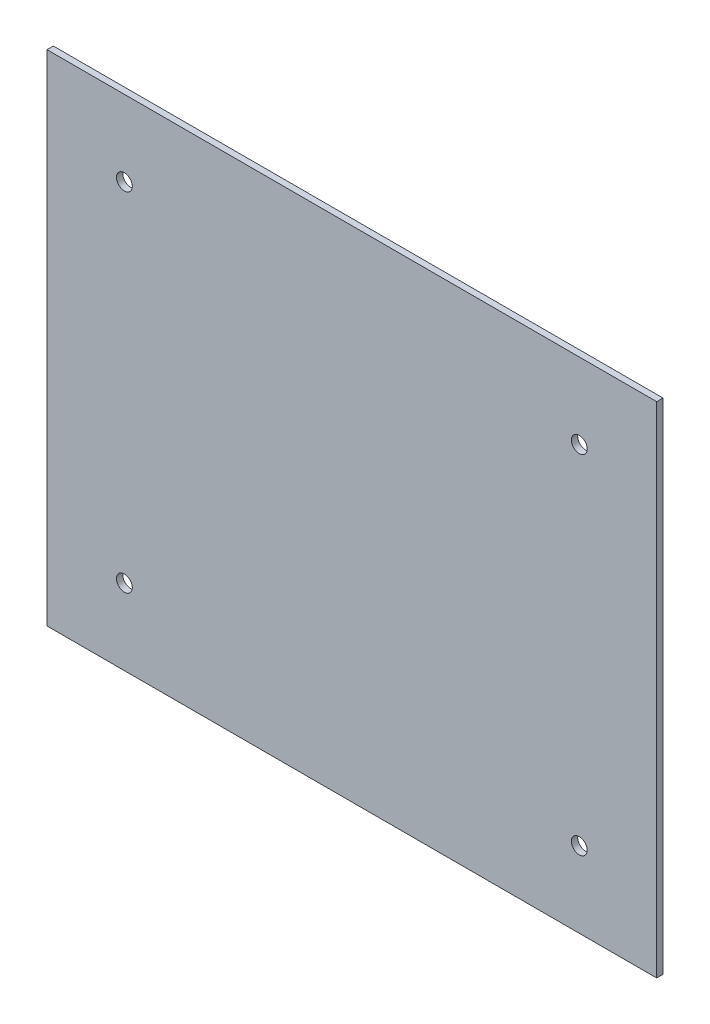
SolidWorks part; units mm, degrees
material "201 Annealed Stainless Steel (SS)"
ref_plane "Front Plane" through (0, 0, 0) normal (0, 0, 1) x (1, 0, 0)
ref_plane "Top Plane" through (0, 0, 0) normal (0, 1, 0) x (1, 0, 0)
ref_plane "Right Plane" through (0, 0, 0) normal (1, 0, 0) x (0, 0, -1)
sketch "Sketch1" plane through (0, 0, 0) normal (0, 0, 1) x (1, 0, 0)
  line L0 (0, 0) -> (0, -146.4794) construction
  line L1 (-96.5, 79) -> (96.5, 79)
  line L2 (-96.5, 79) -> (-96.5, -79)
  line L3 (-96.5, -79) -> (96.5, -79)
  line L4 (96.5, 79) -> (96.5, -79)
  line L5 (-96.5, 79) -> (96.5, -79) construction
  line L6 (-96.5, -79) -> (96.5, 79) construction
  line L7 (0, 0) -> (-417.8368, 0) construction
  circle A0 centre (0, 55) radius 3
  circle A1 centre (-372, 55) radius 3
  circle A2 centre (-372, -55) radius 3
  circle A3 centre (0, -55) radius 3
  circle A4 centre (372, -55) radius 3
  circle A5 centre (372, 55) radius 3
  circle A6 centre (-372, 55) radius 2.5 construction
  point P0 (0, 0)
  dimension "D3" = 6
  dimension "D5" = 21
  dimension "D7" = 272.5
  dimension "D1" = 158
  dimension "D2" = 193
extrude "Boss-Extrude1" add sketch "Sketch1" along normal mid plane 2
other "DeleteFace1" face at (3, 55, 1) face at (-3, -55, 1) and patch yes
sketch "Sketch2" [suppressed] plane through (0, 0, 1) normal (0, 0, 1) x (1, 0, 0)
  line L0 (265.7847, 0) -> (416.352, 0) construction
  line L5 (293.206, -45.5) -> (314.206, -45.5)
  line L6 (293.206, -45.5) -> (293.206, -14.5)
  line L11 (293.206, -14.5) -> (314.206, -14.5)
  line L12 (50.7847, -22.5) -> (95.7847, -22.5)
  line L13 (-93.5, 36.6025) -> (-110.25, 36.6025)
  line L14 (-110.25, 36.6025) -> (-110.25, -45.8975)
  line L15 (-110.25, -45.8975) -> (-49.75, -45.8975)
  line L16 (-49.75, -45.8975) -> (-49.75, 36.6025)
  line L17 (-49.75, 36.6025) -> (-66.5, 36.6025)
  line L18 (-93.5, 36.6025) -> (-110.25, 36.6025)
  line L19 (-110.25, 36.6025) -> (-110.25, -45.8975)
  line L20 (-110.25, -45.8975) -> (-49.75, -45.8975)
  line L21 (-49.75, -45.8975) -> (-49.75, 36.6025)
  line L22 (-49.75, 36.6025) -> (-66.5, 36.6025)
  line L23 (50.7847, 22.5) -> (50.7847, -22.5)
  line L24 (95.7847, 22.5) -> (50.7847, 22.5)
  line L25 (95.7847, -22.5) -> (95.7847, 22.5)
  line L26 (50.7847, -22.5) -> (95.7847, -22.5)
  line L27 (50.7847, 22.5) -> (50.7847, -22.5)
  line L28 (95.7847, 22.5) -> (50.7847, 22.5)
  line L29 (95.7847, -22.5) -> (95.7847, 22.5)
  line L30 (135.7847, -22.5) -> (180.7847, -22.5)
  line L31 (135.7847, 22.5) -> (135.7847, -22.5)
  line L32 (180.7847, 22.5) -> (135.7847, 22.5)
  line L33 (180.7847, -22.5) -> (180.7847, 22.5)
  line L34 (135.7847, -22.5) -> (180.7847, -22.5)
  line L35 (135.7847, 22.5) -> (135.7847, -22.5)
  line L36 (180.7847, 22.5) -> (135.7847, 22.5)
  line L37 (180.7847, -22.5) -> (180.7847, 22.5)
  line L38 (220.7847, -22.5) -> (265.7847, -22.5)
  line L39 (220.7847, 22.5) -> (220.7847, -22.5)
  line L40 (265.7847, 22.5) -> (220.7847, 22.5)
  line L41 (265.7847, -22.5) -> (265.7847, 22.5)
  line L42 (220.7847, -22.5) -> (265.7847, -22.5)
  line L43 (220.7847, 22.5) -> (220.7847, -22.5)
  line L44 (265.7847, 22.5) -> (220.7847, 22.5)
  line L45 (265.7847, -22.5) -> (265.7847, 22.5)
  line L46 (314.206, -45.5) -> (314.206, -14.5)
  line L47 (293.206, -45.5) -> (314.206, -14.5) construction
  line L48 (293.206, -14.5) -> (314.206, -45.5) construction
  line L49 (83.36, 0) -> (-83.36, 0) construction
  line L104 (293.206, -45.5) -> (314.206, -45.5)
  line L105 (293.206, -14.5) -> (293.206, -45.5)
  line L106 (314.206, -14.5) -> (293.206, -14.5)
  line L107 (314.206, -45.5) -> (314.206, -14.5)
  line L108 (293.206, -45.5) -> (314.206, -45.5) construction
  line L109 (293.206, -14.5) -> (293.206, -45.5) construction
  line L110 (314.206, -14.5) -> (293.206, -14.5) construction
  line L111 (314.206, -45.5) -> (314.206, -14.5) construction
  line L165 (-150.5, -45.5) -> (-129.5, -45.5)
  line L166 (-150.5, -14.5) -> (-150.5, -45.5)
  line L167 (-129.5, -14.5) -> (-150.5, -14.5)
  line L168 (-129.5, -45.5) -> (-129.5, -14.5)
  line L169 (-150.5, -45.5) -> (-129.5, -45.5)
  line L170 (-150.5, -14.5) -> (-150.5, -45.5)
  line L171 (-129.5, -14.5) -> (-150.5, -14.5)
  line L172 (-129.5, -45.5) -> (-129.5, -14.5)
  circle A0 centre (303.706, 30) radius 11
  arc A1 (-66.5, 36.6025) -> (-93.5, 36.6025) centre (-80, 35.5625) ccw
  arc A2 (-66.5, 36.6025) -> (-93.5, 36.6025) centre (-80, 35.5625) ccw
  point P25 (303.706, -30)
  dimension "D7" = 22
  dimension "D1" = 0
  dimension "D2" = 0
  dimension "D8" = 30
  dimension "D9" = 30
  dimension "D3" = 0
  dimension "D4" = 0
  dimension "D5" = 0
  dimension "D6" = 0
extrude "Cut-Extrude1" [suppressed] cut sketch "Sketch2" against normal through all
sketch "Sketch3" plane through (0, 0, 1) normal (0, 0, 1) x (1, 0, 0)
  line L0 (0, 0) -> (0, -109.0497) construction
  circle A0 centre (-72, 55) radius 2.5
  circle A1 centre (72, -55) radius 2.5
  circle A2 centre (72, -55) radius 2.5
  circle A3 centre (72, 55) radius 2.5
  circle A4 centre (72, 55) radius 2.5
  circle A5 centre (-72, -55) radius 2.5
  dimension "D1" = 0
  dimension "D2" = 0
extrude "Cut-Extrude2" cut sketch "Sketch3" against normal through all
delete or keep bodies "Body-Delete/Keep 1" type delete bodies bodies 102 103 104 105
other "DeleteFace2" [suppressed]
sketch "Sketch4" [suppressed] plane through (0, 0, 1) normal (0, 0, 1) x (1, 0, 0)
  line L1 (-44.8038, 33) -> (-55.1962, 33) construction
  line L2 (-55.1962, 33) -> (-60.3923, 24) construction
  line L3 (-60.3923, 24) -> (-55.1962, 15) construction
  line L4 (-55.1962, 15) -> (-44.8038, 15) construction
  line L5 (-44.8038, 15) -> (-39.6077, 24) construction
  line L6 (-39.6077, 24) -> (-44.8038, 33) construction
  line L9 (58.2272, -36.75) -> (41.7728, -36.75) construction
  line L10 (41.7728, -36.75) -> (33.5455, -51) construction
  line L11 (33.5455, -51) -> (41.7728, -65.25) construction
  line L12 (41.7728, -65.25) -> (58.2272, -65.25) construction
  line L13 (58.2272, -65.25) -> (66.4545, -51) construction
  line L14 (66.4545, -51) -> (58.2272, -36.75) construction
  line L15 (-44.8038, 8) -> (-55.1962, 8) construction
  line L16 (-55.1962, 8) -> (-60.3923, -1) construction
  line L17 (-60.3923, -1) -> (-55.1962, -10) construction
  line L18 (-55.1962, -10) -> (-44.8038, -10) construction
  line L19 (-44.8038, -10) -> (-39.6077, -1) construction
  line L20 (-39.6077, -1) -> (-44.8038, 8) construction
  circle A0 centre (50, -16) radius 11
  circle A1 centre (50, -51) radius 11
  circle A2 centre (-50, -51) radius 6.5
  circle A3 centre (-50, -26) radius 6.5
  circle A4 centre (-50, -1) radius 6.5
  circle A5 centre (-50, 24) radius 6.5
  circle A6 centre (-50, 24) radius 9 construction
  circle A7 centre (50, -51) radius 14.25 construction
  circle A8 centre (-50, -1) radius 9 construction
  circle A9 centre (-50, -1) radius 10.3923 construction
  circle A10 centre (-50, 24) radius 10.3923 construction
  circle A11 centre (50, -51) radius 16.4545 construction
  dimension "D1" = 22
  dimension "D2" = 13
  dimension "D3" = 25
  dimension "D10" = 35
  dimension "D11" = 16
  dimension "D4" = 18
  dimension "D5" = 50
  dimension "D6" = 50
  dimension "D7" = 28.5
  dimension "D8" = 25
  dimension "D9" = 25
extrude "Cut-Extrude3" [suppressed] cut sketch "Sketch4" against normal through all
sketch "Sketch5" [suppressed] plane through (0, 0, 1) normal (0, 0, 1) x (1, 0, 0)
  circle A0 centre (0, -20) radius 5
  circle A1 centre (0, -40) radius 20 construction
  dimension "D1" = 10
  dimension "D2" = 40
  dimension "D3" = 0
  dimension "D4" = 35
ref_axis "Axis1" [suppressed] through (0, -40, 1) along (0, 0, 1)
extrude "Cut-Extrude4" [suppressed] cut sketch "Sketch5" against normal blind 10
pattern_circular "CirPattern1" [suppressed] count 6 over 360 about axis through (0, -40, 1) along (0, 0, 1) of bodies 111
